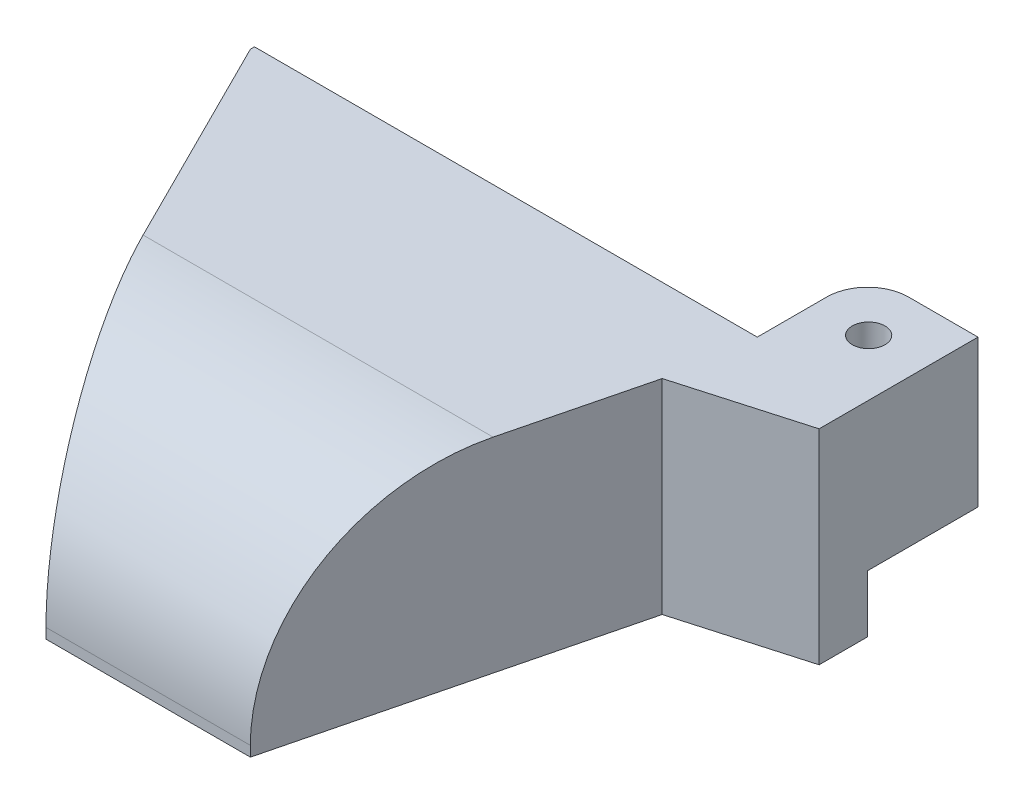
SolidWorks part; units mm, degrees
ref_plane "前视基准面" through (0, 0, 0) normal (0, 0, 1) x (1, 0, 0)
ref_plane "上视基准面" through (0, 0, 0) normal (0, 1, 0) x (1, 0, 0)
ref_plane "右视基准面" through (0, 0, 0) normal (1, 0, 0) x (0, 0, -1)
other "Configuration Table"
sketch "草图1" plane through (0, 0, 0) normal (0, 1, 0) x (1, 0, 0)
  line L1 (0, 0) -> (30, 0)
  line L2 (0, 0) -> (0, -6)
  line L3 (0, -6) -> (30, -6)
  line L4 (30, 0) -> (30, -6)
  dimension "D1" = 30
  dimension "D2" = 6
extrude "凸台-拉伸1" add sketch "草图1" along normal blind 2
sketch "草图2" plane through (0, 2, 0) normal (0, 1, 0) x (1, 0, 0)
  line L0 (30, -6) -> (30, 0) construction
  line L1 (30, 0) -> (0, 0) construction
  circle A0 centre (27.25, -3) radius 0.8
  dimension "D2" = 1.6
  dimension "D3" = 3
  dimension "D1" = 2.75
extrude "切除-拉伸1" cut sketch "草图2" against normal blind 2
sketch "草图3" plane through (0, 2, 0) normal (0, 1, 0) x (1, 0, 0)
  line L0 (0, 0) -> (0, -6) construction
  line L1 (0, -5.8) -> (1.6, -5.8)
  line L2 (0, -5.8) -> (0, -6)
  line L3 (0, -6) -> (1.6, -6)
  line L4 (1.6, -5.8) -> (1.6, -6)
  line L5 (0, -6) -> (30, -6) construction
  line L6 (30, 0) -> (0, 0) construction
  line L7 (30, -6) -> (30, 0) construction
  line L8 (23.4, -6) -> (25, -6)
  line L9 (23.4, -6) -> (23.4, -5.8)
  line L10 (23.4, -5.8) -> (25, -5.8)
  line L11 (25, -6) -> (25, -5.8)
  dimension "D1" = 1.6
  dimension "D2" = 5.8
  dimension "D3" = 5.8
  dimension "D4" = 1.6
  dimension "D5" = 5
extrude "凸台-拉伸2" add sketch "草图3" along normal blind 10
sketch "草图4" plane through (0, 12, 0) normal (0, 1, 0) x (1, 0, 0)
  line L1 (1.6, -5.8) -> (23.4, -5.8)
  line L2 (1.6, -5.8) -> (1.6, -6)
  line L3 (1.6, -6) -> (23.4, -6)
  line L4 (23.4, -5.8) -> (23.4, -6)
extrude "凸台-拉伸3" add sketch "草图4" against normal blind 1.6
sketch "草图5" plane through (0, 2, 0) normal (0, 1, 0) x (1, 0, 0)
  line L1 (25, -5.8) -> (30, -5.8)
  line L2 (25, -5.8) -> (25, -6)
  line L3 (25, -6) -> (30, -6)
  line L4 (30, -5.8) -> (30, -6)
extrude "凸台-拉伸4" add sketch "草图5" along normal blind 10
sketch "草图6" plane through (0, 0, 5.8) normal (0, 0, -1) x (-1, 0, 0)
  line L1 (-30, 12) -> (-24.6, 12)
  line L2 (-30, 12) -> (-30, 4.8)
  line L3 (-30, 4.8) -> (-24.6, 4.8)
  line L4 (-24.6, 12) -> (-24.6, 4.8)
  dimension "D1" = 5.4
  dimension "D2" = 7.2
extrude "凸台-拉伸5" add sketch "草图6" along normal blind 5.4
fillet "圆角1" radius 2 1 edges at (24.6, 8.4, 0.4)
sketch "草图7" plane through (0, 4.8, 0) normal (0, -1, 0) x (-1, 0, 0)
  circle A0 centre (-27.25, -3) radius 0.8
extrude "切除-拉伸2" cut sketch "草图7" against normal through all
sketch "草图8" plane through (0, 0, 0) normal (-1, 0, 0) x (0, 0, 1)
  line L1 (0, 2) -> (6, 2)
  line L2 (0, 2) -> (0, 0)
  line L3 (0, 0) -> (6, 0)
  line L4 (6, 2) -> (6, 0)
extrude "切除-拉伸3" cut sketch "草图8" against normal through all
sketch "草图9" plane through (0, 0, 6) normal (0, 0, 1) x (1, 0, 0)
  line L0 (23.4, 10.4) -> (23.4, 2) construction
  line L1 (1.6, 2) -> (23.4, 2)
  line L2 (1.6, 2) -> (1.6, 3.6)
  line L3 (1.6, 3.6) -> (23.4, 3.6)
  line L4 (23.4, 2) -> (23.4, 3.6)
  dimension "D1" = 1.6
extrude "凸台-拉伸7" add sketch "草图9" against normal up to surface (0.2 mm away) up to face at (15.92, 6.24, 5.8)
ref_plane "分割" through (0, 0, 6) normal (0, 0, 1) x (1, 0, 0)
sketch "草图11" plane through (0, 2, 0) normal (0, -1, 0) x (-1, 0, 0)
  line L0 (0, -6) -> (-10, -26)
  line L1 (-10, -26) -> (-20, -26)
  line L2 (-20, -26) -> (-25, -6)
  line L3 (0, -6) -> (-30, -6) construction
  line L4 (-25, -6) -> (0, -6)
  point P7 (-15, -26)
  dimension "D3" = 20
  dimension "D1" = 1.6
  dimension "D4" = 10
  dimension "D2" = 15
extrude "凸台-拉伸9" add sketch "草图11" against normal blind 1.6
sketch "草图12" plane through (0, 3.6, 0) normal (0, 1, 0) x (1, 0, 0)
  line L11 (2.5889, -7.6) -> (10.9889, -24.4)
  line L12 (10.9889, -24.4) -> (18.7508, -24.4)
  line L13 (18.7508, -24.4) -> (22.9508, -7.6)
  line L16 (23.4, -5.8) -> (1.6, -5.8)
  line L17 (1.6, -5.8) -> (1.6, -6)
  line L18 (1.6, -6) -> (0, -6)
  line L19 (0, -6) -> (10, -26)
  line L20 (10, -26) -> (20, -26)
  line L21 (20, -26) -> (25, -6)
  line L22 (25, -6) -> (23.4, -6)
  line L23 (23.4, -6) -> (23.4, -5.8)
  line L26 (1.6, -6) -> (0, -6)
  line L27 (0, -6) -> (10, -26)
  line L28 (10, -26) -> (20, -26)
  line L29 (20, -26) -> (25, -6)
  line L30 (25, -6) -> (23.4, -6)
  line L32 (2.5889, -7.6) -> (1.6, -6)
  line L33 (22.9508, -7.6) -> (23.4, -6)
  line L35 (21.8, -7.4) -> (3.2, -7.4) construction
  line L36 (21.8, -7.6) -> (21.8, -7.4) construction
  line L37 (22.9508, -7.6) -> (21.8, -7.6) construction
  line L38 (23.4, -5.8) -> (1.6, -5.8) construction
  line L39 (23.4, -6) -> (23.4, -5.8) construction
  line L40 (3.2, -7.6) -> (2.5889, -7.6) construction
  line L41 (3.2, -7.4) -> (3.2, -7.6) construction
  line L42 (1.6, -5.8) -> (1.6, -6) construction
  dimension "D1" = 0
  dimension "D2" = 1.6
extrude "凸台-拉伸10" add sketch "草图12" along normal up to surface (8.4 mm away) up to face at (27.25, 12, 2.2)
sketch "草图13" plane through (0, 12, 0) normal (0, 1, 0) x (1, 0, 0)
  line L16 (1.6, -5.8) -> (1.6, -6)
  line L17 (1.6, -6) -> (2.5889, -7.6)
  line L18 (2.5889, -7.6) -> (10.9889, -24.4)
  line L19 (10.9889, -24.4) -> (18.7508, -24.4)
  line L20 (18.7508, -24.4) -> (22.9508, -7.6)
  line L21 (22.9508, -7.6) -> (23.4, -6)
  line L22 (23.4, -6) -> (23.4, -5.8)
  line L23 (23.4, -5.8) -> (1.6, -5.8)
  line L24 (1.6, -5.8) -> (1.6, -6)
  line L25 (1.6, -6) -> (2.5889, -7.6)
  line L26 (2.5889, -7.6) -> (10.9889, -24.4)
  line L27 (10.9889, -24.4) -> (18.7508, -24.4)
  line L28 (18.7508, -24.4) -> (22.9508, -7.6)
  line L29 (22.9508, -7.6) -> (23.4, -6)
  line L30 (23.4, -6) -> (23.4, -5.8)
  line L31 (23.4, -5.8) -> (1.6, -5.8)
  dimension "D1" = 0
extrude "凸台-拉伸11" add sketch "草图13" against normal blind 1.6
sketch "草图15" plane through (0, 2, 0) normal (0, -1, 0) x (1, 0, 0)
  line L0 (10.9889, 24.4) -> (18.7508, 24.4)
  line L1 (18.7508, 24.4) -> (19.7508, 20.4)
  line L2 (19.7508, 20.4) -> (8.9889, 20.4)
  line L3 (8.9889, 20.4) -> (10.9889, 24.4)
  line L4 (20, 26) -> (10, 26) construction
  line L5 (10, 26) -> (0, 6) construction
  line L6 (25, 6) -> (20, 26) construction
  dimension "D1" = 1.6
  dimension "D2" = 180
  dimension "D3" = 180
  dimension "D4" = 1.6
  dimension "D5" = 1.6
  dimension "D6" = 4
extrude "切除-拉伸4" cut sketch "草图15" against normal blind 1.6
fillet "圆角2" radius 9 1 edges at (14.8698, 10.4, 24.4)
fillet "圆角3" radius 9.5 1 edges at (15, 12, 26)
fillet "圆角4" radius 1 1 edges at (14.3698, 3.6, 20.4)
chamfer "倒角1" distance 4 angle 60 1 edges at (25, 7, 6) first distance on face at (22.3766, 6.4935, 16.4935)
equation "\"D2@草图11\"=\"D1@草图1\"/2"
